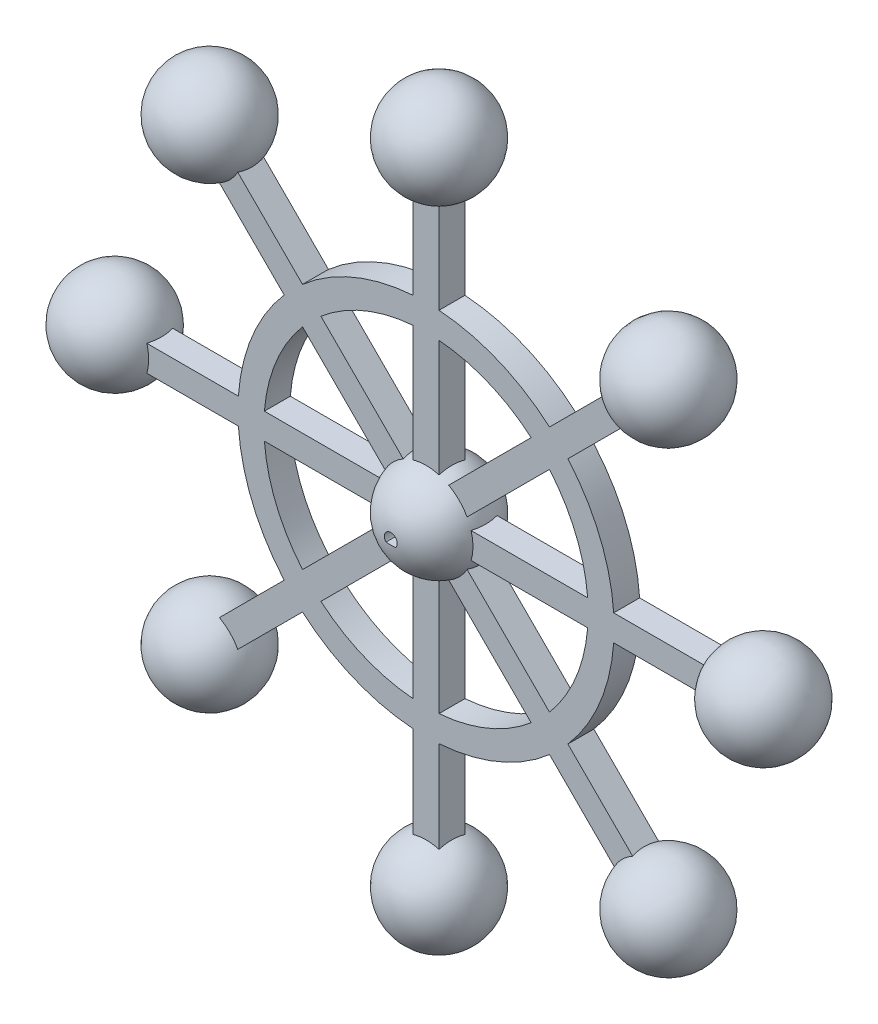
SolidWorks part; units mm, degrees
ref_plane "Front Plane" through (0, 0, 0) normal (0, 0, 1) x (1, 0, 0)
ref_plane "Top Plane" through (0, 0, 0) normal (0, 1, 0) x (1, 0, 0)
ref_plane "Right Plane" through (0, 0, 0) normal (1, 0, 0) x (0, 0, -1)
sketch "Sketch1" plane through (0, 0, 0) normal (0, 0, 1) x (1, 0, 0)
  line L0 (0, 19.05) -> (0, -19.05)
  arc A0 (0, -19.05) -> (0, 19.05) centre (0, 0) ccw
  dimension "D1" = 38.1
revolve "Revolve1" add sketch "Sketch1" angle 360 about L0
sketch "Sketch2" plane through (0, 0, 0) normal (0, 0, 1) x (1, 0, 0)
  line L0 (0, 0) -> (127, 0) construction
  line L1 (0, -5.08) -> (127, -5.08)
  line L2 (0, 5.08) -> (127, 5.08)
  line L3 (127, 5.08) -> (127, -5.08)
  line L4 (0, 5.08) -> (0, -5.08)
  dimension "D1" = 127
  dimension "D2" = 5.08
  dimension "D3" = 5.08
extrude "Boss-Extrude1" add sketch "Sketch2" along normal blind 5.08 and the other way blind 5.08
sketch "Sketch3" plane through (0, 0, 0) normal (0, 1, 0) x (1, 0, 0)
  line L0 (0, 0) -> (0, 8.1282) construction
pattern_circular "CirPattern1" count 8 over 360 about axis through (0, 0, 0) along (0, 0, -1) of "Boss-Extrude1" reverse direction yes
sketch "Sketch5" plane through (0, 0, -5.08) normal (0, 0, -1) x (-1, 0, 0)
  circle A0 centre (0, 0) radius 63.5
  circle A1 centre (0, 0) radius 73.66
  dimension "D1" = 127
  dimension "D2" = 10.16
extrude "Boss-Extrude2" add sketch "Sketch5" against normal blind 10.16
sketch "Sketch6" plane through (0, 0, -5.08) normal (0, 0, -1) x (-1, 0, 0)
  line L0 (-1.8555, -1.6783) -> (1.8555, -1.6783)
  arc A0 (1.8555, -1.6783) -> (-1.8555, -1.6783) centre (0, 0) ccw
  point P5 (0, 0)
  point P6 (0, 0)
  dimension "D1" = 5.0038
  dimension "D2" = 3.711
extrude "Cut-Extrude1" cut sketch "Sketch6" against normal through all and the other way through all
sketch "Sketch7" plane through (0, 0, 0) normal (0, 0, 1) x (1, 0, 0)
  line L0 (5.08, 127) -> (-5.08, 127) construction
  line L1 (0, 107.95) -> (0, 146.05)
  arc A0 (0, 107.95) -> (0, 146.05) centre (0, 127) ccw
  dimension "D1" = 38.1
revolve "Revolve2" add sketch "Sketch7" angle 360 about L1
pattern_circular "CirPattern2" count 8 over 360 about axis through (0, 0, 0) along (0, 0, -1) of "Revolve2"
